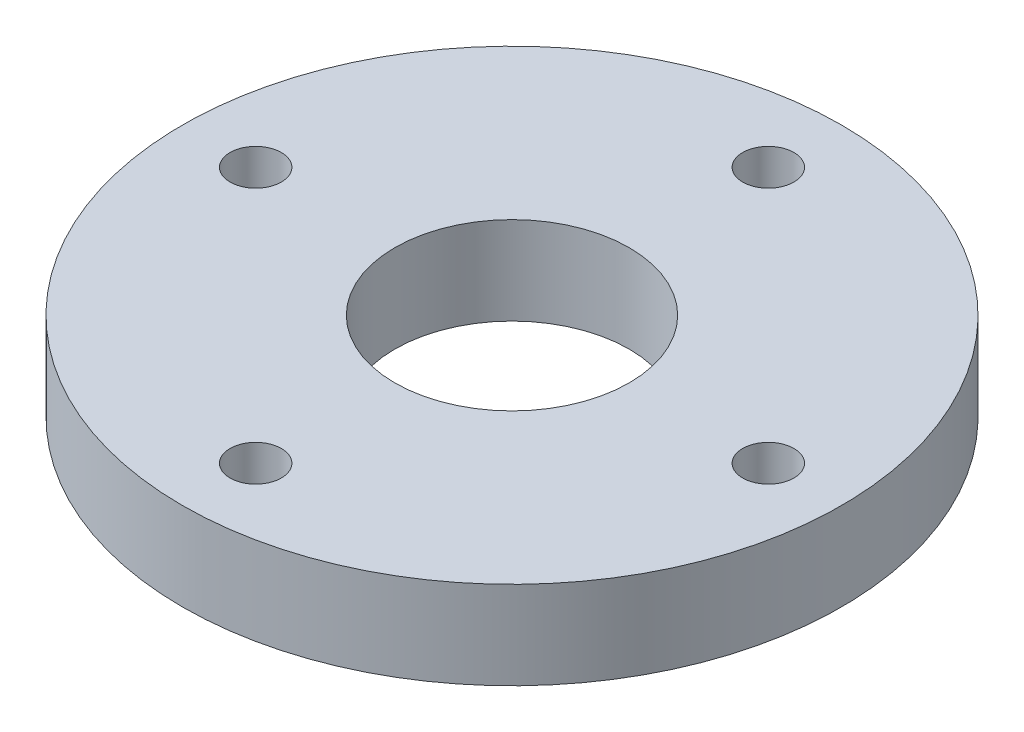
SolidWorks part; units mm, degrees
ref_plane "Front Plane" through (0, 0, 0) normal (0, 0, 1) x (1, 0, 0)
ref_plane "Top Plane" through (0, 0, 0) normal (0, 1, 0) x (1, 0, 0)
ref_plane "Right Plane" through (0, 0, 0) normal (1, 0, 0) x (0, 0, -1)
sketch "Sketch1" plane through (0, 0, 0) normal (0, 1, 0) x (1, 0, 0)
  circle A0 centre (0, 0) radius 22.5
  circle A1 centre (0, 0) radius 8
  dimension "D1" = 45
  dimension "D2" = 16
extrude "Boss-Extrude1" add sketch "Sketch1" along normal blind 6
ref_axis "Axis1" through (0, -0.3, 0) along (0, 1, 0)
sketch "Sketch2" plane through (0, 6, 0) normal (0, 1, 0) x (1, 0, 0)
  line L0 (0, 0) -> (0, 23.8273) construction
  circle A0 centre (0, 17.5) radius 1.75
  dimension "D1" = 3.5
  dimension "D2" = 17.5
extrude "Cut-Extrude1" cut sketch "Sketch2" against normal blind 6
cosmetic thread "Cosmetic Thread4" parameters "D2"=5
pattern_circular "CirPattern1" count 4 over 360 about axis through (0, -0.3, 0) along (0, 1, 0) of "Cut-Extrude1"
cosmetic thread "Cosmetic Thread2" parameters "D2"=5
cosmetic thread "Cosmetic Thread3" parameters "D2"=5
cosmetic thread "Cosmetic Thread5" parameters "D2"=5
sketch "Sketch3" plane through (0, 0, 0) normal (0, -1, 0) x (-1, 0, 0)
  line L0 (-12.9122, -12.9122) -> (0, 0) construction
  line L1 (0, 0) -> (-28.0354, 0) construction
  circle A0 centre (0, 0) radius 14.5 construction
  circle A1 centre (-10.253, -10.253) radius 0.75
  dimension "D1" = 29
  dimension "D3" = 1.5
  dimension "D2" = 45
extrude "Cut-Extrude2" cut sketch "Sketch3" against normal blind 5
cosmetic thread "Cosmetic Thread1" parameters "D2"=2
pattern_circular "CirPattern2" count 3 every 120 about axis through (0, -0.3, 0) along (0, 1, 0) of "Cut-Extrude2"
